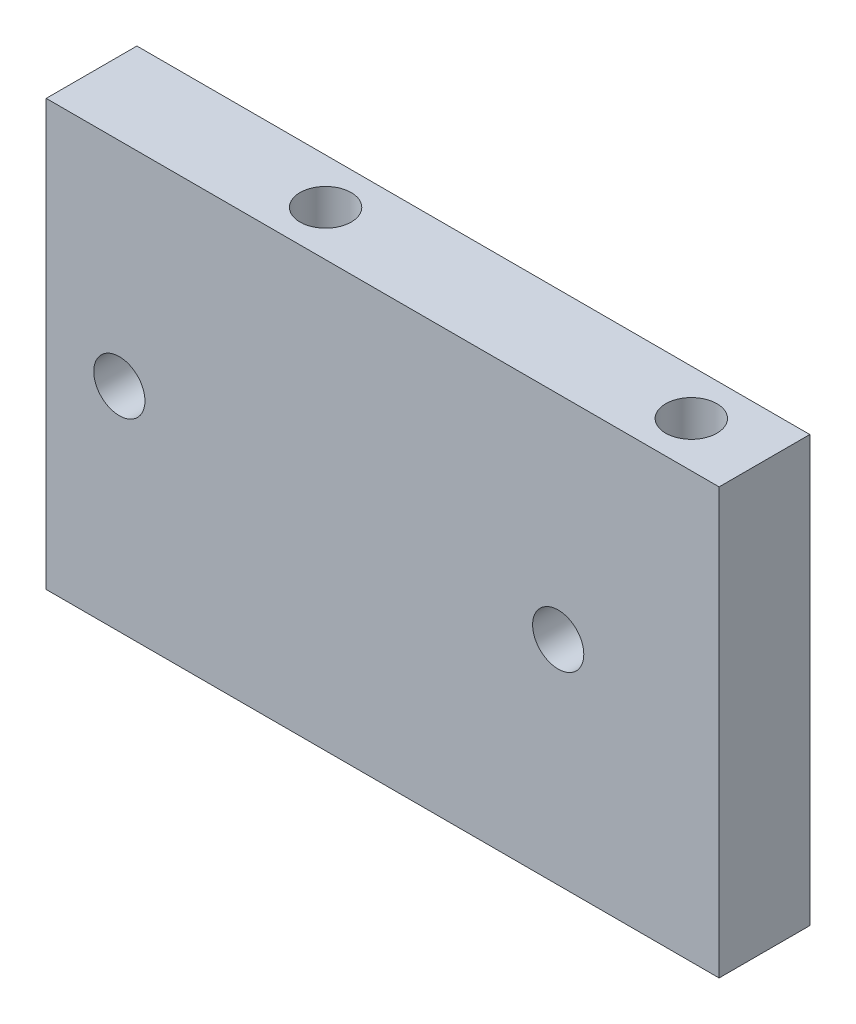
SolidWorks part; units mm, degrees
material "6061 Alloy"
ref_plane "Front Plane" through (0, 0, 0) normal (0, 0, 1) x (1, 0, 0)
ref_plane "Top Plane" through (0, 0, 0) normal (0, 1, 0) x (1, 0, 0)
ref_plane "Right Plane" through (0, 0, 0) normal (1, 0, 0) x (0, 0, -1)
sketch "Sketch1" plane through (0, 0, 0) normal (0, 0, 1) x (1, 0, 0)
  line L1 (-23, 14.5375) -> (23, 14.5375)
  line L2 (-23, 14.5375) -> (-23, -14.5375)
  line L3 (-23, -14.5375) -> (23, -14.5375)
  line L4 (23, 14.5375) -> (23, -14.5375)
  line L5 (0, -14.5375) -> (0, 14.5375) construction
  line L6 (-23, 0) -> (23, 0) construction
  point P0 (0, 0)
  dimension "D1" = 29.075
  dimension "D2" = 46
extrude "1/4" add sketch "Sketch1" along normal blind 6.2
sketch "Sketch2" plane through (0, 0, 0) normal (0, 0, 1) x (1, 0, 0)
  line L0 (0, 0) -> (-18, 0) construction
  line L1 (0, 0) -> (0, 8.9877) construction
  line L2 (-23, 14.5375) -> (-23, -14.5375) construction
  circle A0 centre (-18, 0) radius 1.75
  circle A2 centre (12, 0) radius 1.75
  dimension "D2" = 3.5
  dimension "D1" = 5
  dimension "D3" = 2
extrude "M4_DRILL" cut sketch "Sketch2" along normal up to surface (6.2 mm away) up to face at (0, 0, 6.2)
sketch "Sketch3" plane through (0, -14.5375, 0) normal (0, -1, 0) x (1, 0, 0)
  line L0 (-23, 3.1) -> (-7, 3.1) construction
  line L1 (-23, 6.2) -> (-23, 0) construction
  circle A0 centre (-7, 3.1) radius 1.75
  circle A1 centre (18, 3.1) radius 1.75
  dimension "D1" = 3.5
  dimension "D2" = 16
  dimension "D3" = 2
extrude "M4_DRILL2" cut sketch "Sketch3" against normal blind 8
sketch "Sketch4" plane through (0, 14.5375, 0) normal (0, 1, 0) x (1, 0, 0)
  circle A0 centre (18, -3.1) radius 1.75 construction
  circle A1 centre (-7, -3.1) radius 1.75 construction
  circle A2 centre (18, -3.1) radius 1.75
  circle A3 centre (-7, -3.1) radius 1.75
extrude "M4_DRILL3" cut sketch "Sketch4" against normal blind 8
